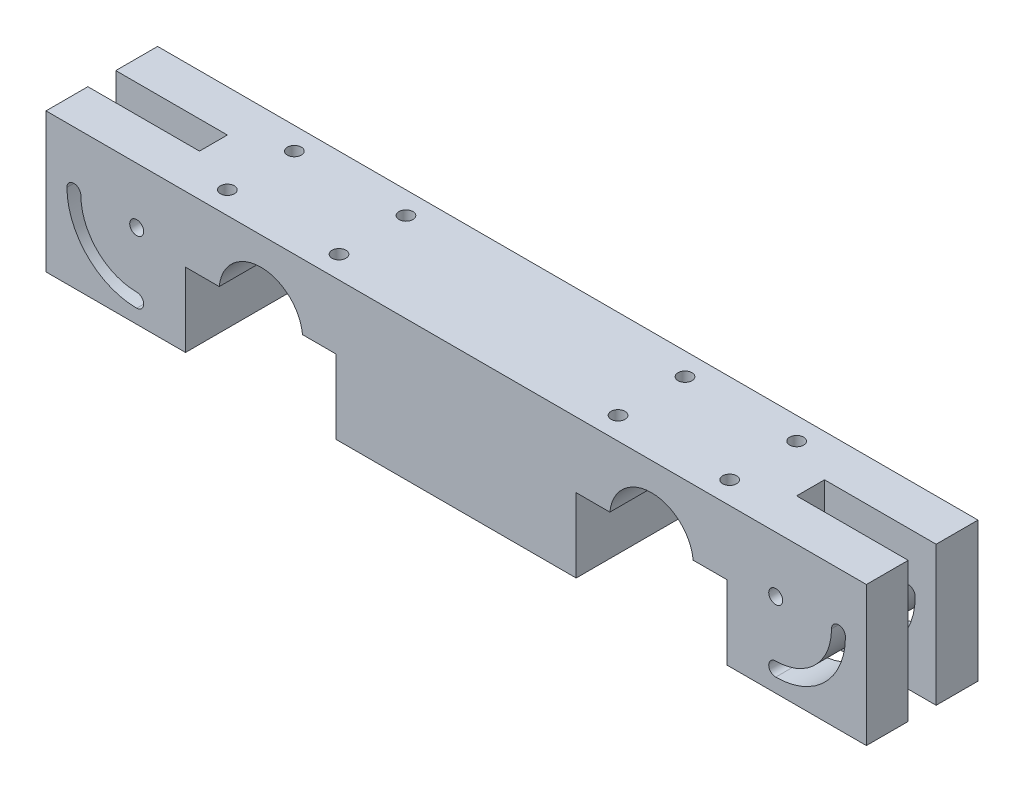
SolidWorks part; units mm, degrees
ref_plane "Front Plane" through (0, 0, 0) normal (0, 0, 1) x (1, 0, 0)
ref_plane "Top Plane" through (0, 0, 0) normal (0, 1, 0) x (1, 0, 0)
ref_plane "Right Plane" through (0, 0, 0) normal (1, 0, 0) x (0, 0, -1)
sketch "Sketch1" plane through (0, 0, 0) normal (0, 0, 1) x (1, 0, 0)
  line L1 (0, 0) -> (147, 0)
  line L2 (0, 0) -> (0, 50)
  line L3 (0, 50) -> (147, 50)
  line L4 (147, 0) -> (147, 50)
  line L5 (23, 50) -> (62, 50)
  line L6 (43, 0) -> (97, 0)
  line L7 (43, 0) -> (43, 26.5)
  line L8 (43, 26.5) -> (97, 26.5)
  line L9 (97, 0) -> (97, 26.5)
  circle A0 centre (70, 25) radius 15
  circle A1 centre (114.5, 30) radius 2.5
  arc A2 (114.5, 5) -> (139.5, 30) centre (114.5, 30) ccw
  arc A3 (114.5, 5) -> (114.5, 10) centre (114.5, 7.5) cw
  arc A4 (139.5, 30) -> (134.5, 30) centre (137, 30) ccw
  arc A5 (114.5, 10) -> (134.5, 30) centre (114.5, 30) ccw
  point P17 (114.5, 7.5)
  point P20 (137, 30)
  dimension "D3" = 30
  dimension "D4" = 25
  dimension "D9" = 5
  dimension "D1" = 50
  dimension "D2" = 50
  dimension "D5" = 70
  dimension "D6" = 26.5
  dimension "D7" = 54
  dimension "D8" = 27
  dimension "D10" = 20
  dimension "D11" = 17.5
  dimension "D12" = 25
  dimension "D13" = 2.5
  dimension "D14" = 2.5
extrude "Boss-Extrude1" add sketch "Sketch1" along normal blind 40 contours A0 L3 L2 L1 L4 region at (1.5527, 25, 0)
sketch "Sketch3" plane through (0, 50, 0) normal (0, 1, 0) x (1, 0, 0)
  line L0 (0, -40) -> (147, -40) construction
  line L1 (0, -40) -> (0, 0) construction
  line L2 (0, 0) -> (147, 0) construction
  circle A0 centre (50, -32) radius 2.5
  circle A1 centre (90, -32) radius 2.5
  circle A2 centre (50, -8) radius 2.5
  circle A3 centre (90, -8) radius 2.5
  dimension "D2" = 5
  dimension "D5" = 5
  dimension "D7" = 5
  dimension "D8" = 5
  dimension "D1" = 8
  dimension "D3" = 50
  dimension "D4" = 8
  dimension "D6" = 90
  dimension "D9" = 50
  dimension "D10" = 8
  dimension "D11" = 8
  dimension "D12" = 90
extrude "Cut-Extrude2" cut sketch "Sketch3" against normal up to surface (23.5 mm away) up to face at (49.0376, 26.5, 20)
sketch "Sketch4" plane through (0, 50, 0) normal (0, 1, 0) x (1, 0, 0)
  line L0 (147, -40) -> (147, 0) construction
  line L1 (147, -15) -> (107, -15)
  line L2 (147, -15) -> (147, -25)
  line L3 (147, -25) -> (107, -25)
  line L4 (107, -15) -> (107, -25)
  line L5 (0, 0) -> (147, 0) construction
  dimension "D1" = 40
  dimension "D2" = 10
  dimension "D3" = 15
extrude "Cut-Extrude3" cut sketch "Sketch4" against normal up to surface (50 mm away) up to face at (122, 0, 20)
mirror "Mirror2" about plane through (0, 0, 40) normal (-1, 0, 0) of "Cut-Extrude2", "Cut-Extrude3", "Boss-Extrude1"
